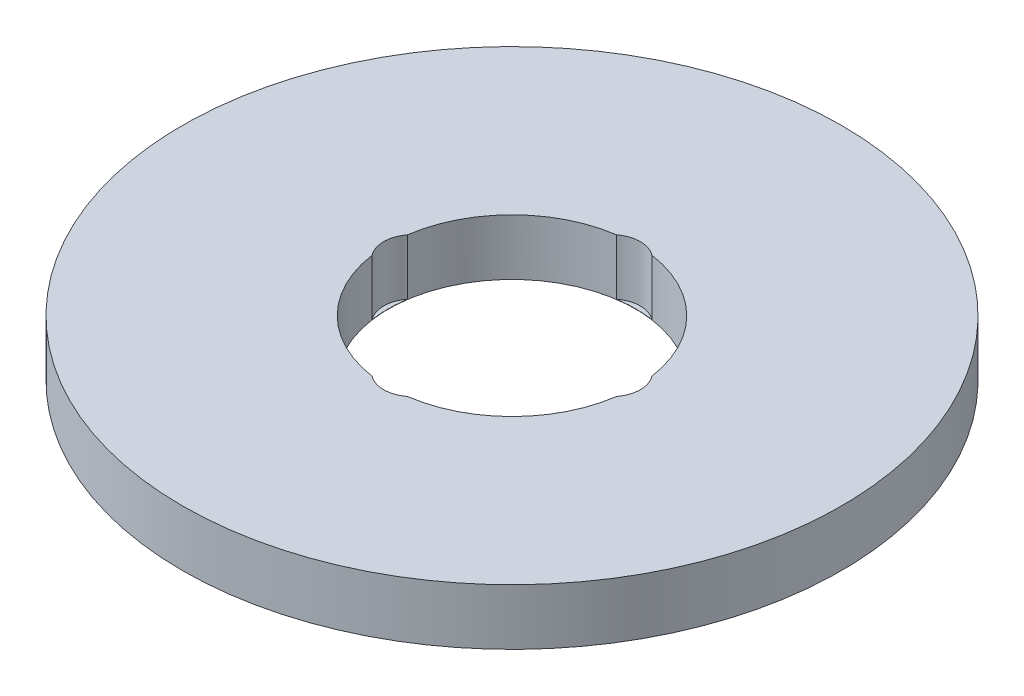
SolidWorks part; units mm, degrees
ref_plane "Front Plane" through (0, 0, 0) normal (0, 0, 1) x (1, 0, 0)
ref_plane "Top Plane" through (0, 0, 0) normal (0, 1, 0) x (1, 0, 0)
ref_plane "Right Plane" through (0, 0, 0) normal (1, 0, 0) x (0, 0, -1)
sketch "Sketch1" plane through (0, 0, 0) normal (0, 1, 0) x (1, 0, 0)
  circle A0 centre (0, 0) radius 100
  dimension "FLANGE_OD" = 200
extrude "Boss-Extrude1" add sketch "Sketch1" along normal blind 17
sketch "Sketch2" plane through (0, 0, 0) normal (0, 1, 0) x (1, 0, 0)
  circle A0 centre (0, 0) radius 37.5
  dimension "BORE_D" = 75
extrude "Cut-Extrude1" cut sketch "Sketch2" along normal through all
sketch "Sketch3" plane through (0, 17, 0) normal (0, 1, 0) x (1, 0, 0)
  circle A0 centre (0, 0) radius 30.1262 construction
  circle A1 centre (-30.1262, 0) radius 8.8058
  dimension "BOLT_D" = 17.6116
  dimension "BOLT_PCD" = 60.2524
extrude "Cut-Extrude2" cut sketch "Sketch3" against normal blind 16.9181
pattern_circular "CirPattern1" count 4 over 360 about axis through (0, 0, 0) along (0, 1, 0) of "Cut-Extrude2"
